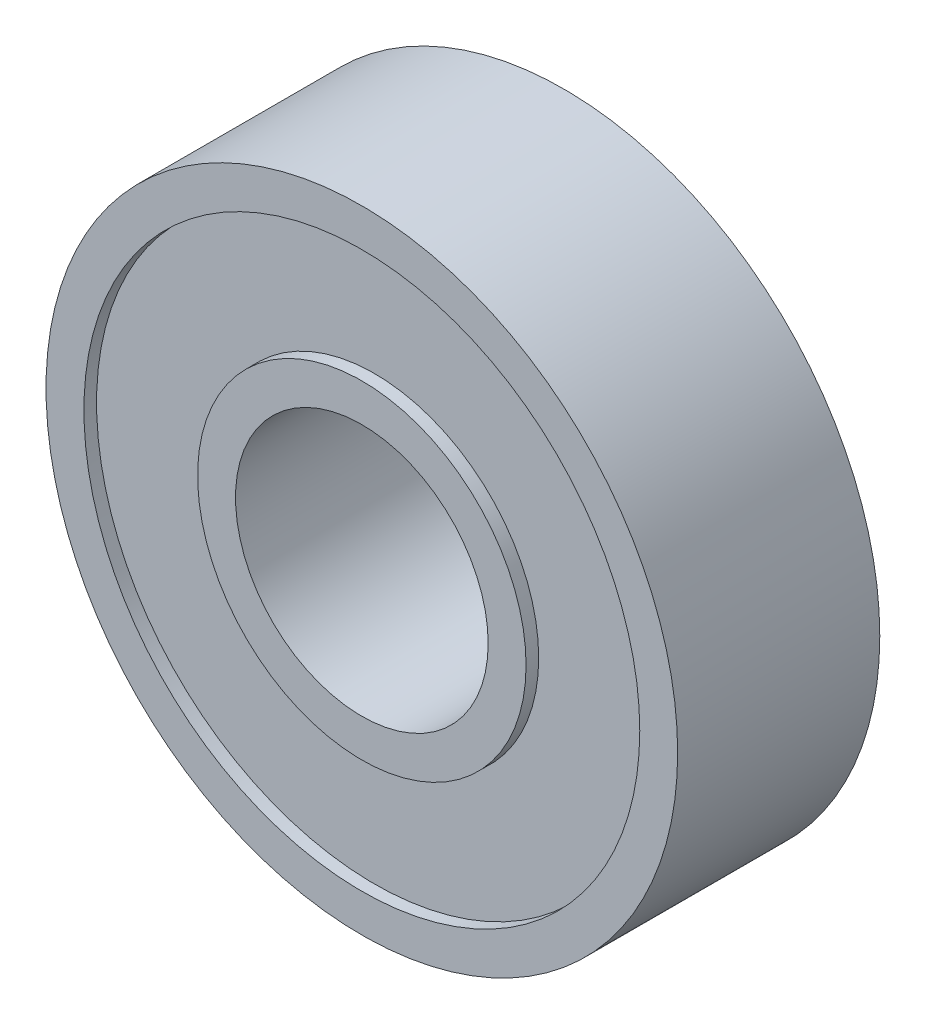
SolidWorks part; units mm, degrees
ref_plane "Alzado" through (0, 0, 0) normal (0, 0, 1) x (1, 0, 0)
ref_plane "Planta" through (0, 0, 0) normal (0, 1, 0) x (1, 0, 0)
ref_plane "Vista lateral" through (0, 0, 0) normal (1, 0, 0) x (0, 0, -1)
sketch "Croquis1" plane through (0, 0, 0) normal (0, 0, 1) x (1, 0, 0)
  circle A0 centre (0, 0) radius 12.5
  circle A1 centre (0, 0) radius 5
  circle A2 centre (0, 0) radius 11
  circle A3 centre (0, 0) radius 6.5
  dimension "D1" = 25
  dimension "D2" = 10
  dimension "D3" = 1.5
  dimension "D4" = 1.5
extrude "Saliente-Extruir1" add sketch "Croquis1" along normal blind 4 and the other way blind 4 contours A0 A2 | A3 A1 region at (-12.1464, 0, 0) region at (-6.3162, 0, 0)
extrude "Saliente-Extruir2" add sketch "Croquis1<4>" along normal blind 3.5 and the other way blind 3.5 contours A2 A3 region at (-10.6889, 0, 0)
sketch "Croquis1<4>" plane through (0, 0, 0) normal (0, 0, 1) x (1, 0, 0) same geometry as "Croquis1"
